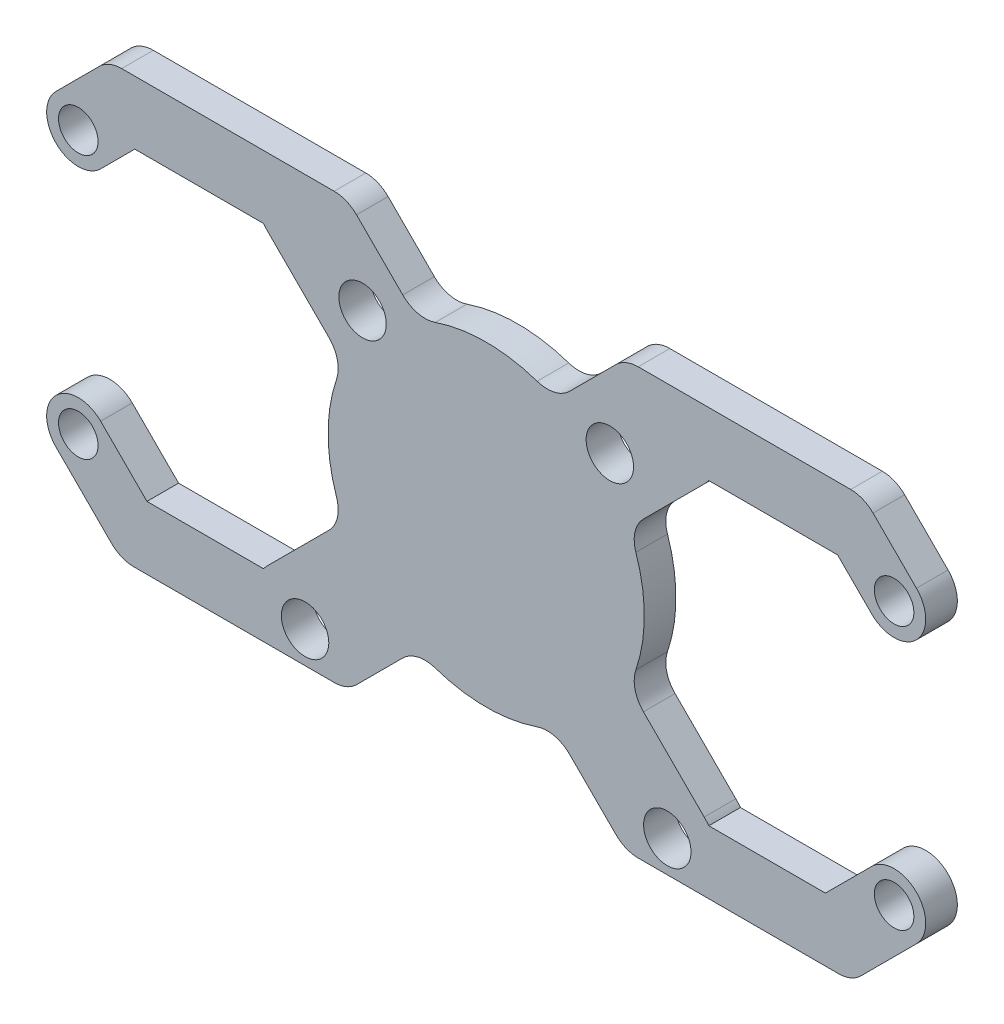
SolidWorks part; units mm, degrees
ref_plane "Front Plane" through (0, 0, 0) normal (0, 0, 1) x (1, 0, 0)
ref_plane "Top Plane" through (0, 0, 0) normal (0, 1, 0) x (1, 0, 0)
ref_plane "Right Plane" through (0, 0, 0) normal (1, 0, 0) x (0, 0, -1)
sketch "Sketch1" plane through (0, 0, 0) normal (0, 0, 1) x (1, 0, 0)
  line L0 (0, -58.2599) -> (0, -50.4392) construction
  line L1 (26.4388, -50.4392) -> (-26.4388, -50.4392) construction
  line L2 (11.4551, -46.8048) -> (23.0548, -46.8048) construction
  line L3 (6.6186, -49.2371) -> (9.0228, -51.6413) construction
  line L4 (11.4551, -44.8048) -> (23.0548, -44.8048)
  line L5 (12.6572, -48.0069) -> (7.7075, -52.9566) construction
  line L6 (5.3033, -50.5524) -> (10.253, -45.6027) construction
  line L7 (-9.0228, -51.6413) -> (-6.6186, -49.2371) construction
  line L8 (-10.253, -45.6027) -> (-5.3033, -50.5524) construction
  line L9 (-7.7075, -52.9566) -> (-12.6572, -48.0069) construction
  line L10 (9.9463, -52.9805) -> (13.7886, -49.1382)
  line L26 (11.4551, -48.8048) -> (23.0548, -48.8048)
  line L27 (23.0548, -46.8048) -> (25.8, -49.55) construction
  line L28 (24.469, -45.3906) -> (27.2142, -48.1358)
  line L29 (21.6406, -48.219) -> (24.3858, -50.9642)
  line L30 (27.5, -54.0885) -> (24.8808, -51.4692) construction
  line L31 (9.9463, -52.9805) -> (13.7886, -49.1382)
  line L39 (-11.4551, -46.8048) -> (-23.0548, -46.8048) construction
  line L40 (-11.4551, -48.8048) -> (-23.0548, -48.8048)
  line L41 (-11.4551, -44.8048) -> (-23.0548, -44.8048)
  line L42 (-23.0548, -46.8048) -> (-25.8, -49.55) construction
  line L43 (-21.6406, -48.219) -> (-24.3858, -50.9642)
  line L44 (-24.469, -45.3906) -> (-27.2142, -48.1358)
  line L45 (-27.5, -54.0885) -> (-24.8808, -51.4692) construction
  line L46 (39.7884, -58.2599) -> (-39.7884, -58.2599) construction
  line L47 (0, -58.2599) -> (0, -69.715) construction
  line L50 (-11.4551, -69.715) -> (11.4551, -69.715) construction
  line L53 (-29.1, -57.875) -> (0, -57.875) construction
  line L56 (-29.1, -56.6635) -> (-29.1, -59.0865) construction
  line L59 (-11.4551, -69.715) -> (-22.285, -69.715) construction
  line L60 (-11.4551, -71.715) -> (-22.285, -71.715)
  line L61 (-11.4551, -67.715) -> (-22.285, -67.715)
  line L62 (-25.8, -66.2) -> (-22.285, -69.715) construction
  line L63 (-24.3858, -64.7858) -> (-20.8708, -68.3008)
  line L64 (-27.2142, -67.6142) -> (-23.6992, -71.1292)
  line L65 (-29.7192, -63.1192) -> (-27.1, -65.7385) construction
  line L66 (25.8, -66.2) -> (22.285, -69.715) construction
  line L67 (13.7886, -67.3816) -> (9.9463, -63.5393)
  line L71 (13.7886, -67.3816) -> (9.9463, -63.5393)
  line L75 (24.3858, -64.7858) -> (20.8708, -68.3008)
  line L76 (27.2142, -67.6142) -> (23.6992, -71.1292)
  line L77 (11.4551, -69.715) -> (22.285, -69.715) construction
  line L78 (11.4551, -71.715) -> (22.285, -71.715)
  line L79 (11.4551, -67.715) -> (22.285, -67.715)
  line L83 (5.2794, -68.2062) -> (9.1217, -72.0485)
  line L85 (5.2794, -68.2062) -> (9.1217, -72.0485)
  line L87 (-9.1217, -72.0485) -> (-5.2794, -68.2062)
  line L89 (-9.1217, -72.0485) -> (-5.2794, -68.2062)
  line L96 (-9.9463, -63.5393) -> (-13.7886, -67.3816)
  line L97 (-9.9463, -63.5393) -> (-13.7886, -67.3816)
  line L98 (-13.7886, -49.1382) -> (-9.9463, -52.9805)
  line L99 (-13.7886, -49.1382) -> (-9.9463, -52.9805)
  line L100 (-5.2794, -48.3136) -> (-9.1217, -44.4713)
  line L101 (-5.2794, -48.3136) -> (-9.1217, -44.4713)
  line L102 (9.1217, -44.4713) -> (5.2794, -48.3136)
  line L103 (9.1217, -44.4713) -> (5.2794, -48.3136)
  arc A0 (11.4551, -44.8048) -> (11.4551, -48.8048) centre (11.4551, -46.8048) ccw
  circle A1 centre (-7.8207, -50.4392) radius 1.5
  circle A2 centre (7.8207, -50.4392) radius 1.5
  circle A3 centre (11.4551, -69.715) radius 1.5
  circle A4 centre (-11.4551, -69.715) radius 1.5
  circle A5 centre (25.8, -49.55) radius 1.25
  arc A6 (27.1, -49.55) -> (24.5, -49.55) centre (25.8, -49.55) ccw construction
  circle A7 centre (-25.8, -49.55) radius 1.25
  arc A8 (-24.5, -49.55) -> (-27.1, -49.55) centre (-25.8, -49.55) ccw construction
  arc A9 (23.0548, -48.8048) -> (23.0548, -44.8048) centre (23.0548, -46.8048) ccw
  arc A10 (24.469, -45.3906) -> (21.6406, -48.219) centre (23.0548, -46.8048) ccw
  arc A11 (24.3858, -50.9642) -> (27.2142, -48.1358) centre (25.8, -49.55) ccw
  arc A12 (-11.4551, -48.8048) -> (-11.4551, -44.8048) centre (-11.4551, -46.8048) ccw
  arc A13 (-23.0548, -44.8048) -> (-23.0548, -48.8048) centre (-23.0548, -46.8048) ccw
  arc A14 (-21.6406, -48.219) -> (-24.469, -45.3906) centre (-23.0548, -46.8048) ccw
  arc A15 (-27.2142, -48.1358) -> (-24.3858, -50.9642) centre (-25.8, -49.55) ccw
  arc A21 (9.9463, -52.9805) -> (9.3605, -54.3948) centre (11.3605, -54.3948) ccw
  arc A29 (9.9463, -52.9805) -> (9.3605, -54.3948) centre (11.3605, -54.3948) ccw
  arc A37 (9.3605, -54.3948) -> (9.4671, -55.0389) centre (11.3605, -54.3948) ccw
  arc A69 (9.3605, -54.3948) -> (9.4671, -55.0389) centre (11.3605, -54.3948) ccw
  arc A77 (9.4671, -61.4809) -> (9.4671, -55.0389) centre (0, -58.2599) ccw
  arc A85 (9.4671, -61.4809) -> (9.4671, -55.0389) centre (0, -58.2599) ccw
  arc A89 (-11.4551, -71.715) -> (-11.4551, -67.715) centre (-11.4551, -69.715) ccw
  arc A90 (-22.285, -67.715) -> (-22.285, -71.715) centre (-22.285, -69.715) ccw
  circle A91 centre (-25.8, -66.2) radius 1.25
  arc A92 (-27.1, -66.2) -> (-24.5, -66.2) centre (-25.8, -66.2) ccw construction
  arc A93 (-24.3858, -64.7858) -> (-27.2142, -67.6142) centre (-25.8, -66.2) ccw
  arc A94 (-23.6992, -71.1292) -> (-20.8708, -68.3008) centre (-22.285, -69.715) ccw
  circle A95 centre (25.8, -66.2) radius 1.25
  arc A96 (24.3858, -64.7858) -> (27.2142, -67.6142) centre (25.8, -66.2) cw
  arc A97 (23.6992, -71.1292) -> (20.8708, -68.3008) centre (22.285, -69.715) cw
  arc A98 (11.4551, -71.715) -> (11.4551, -67.715) centre (11.4551, -69.715) cw
  arc A99 (22.285, -67.715) -> (22.285, -71.715) centre (22.285, -69.715) cw
  arc A113 (9.4671, -61.4809) -> (9.3605, -62.1251) centre (11.3605, -62.1251) ccw
  arc A117 (9.4671, -61.4809) -> (9.3605, -62.1251) centre (11.3605, -62.1251) ccw
  arc A121 (9.3605, -62.1251) -> (9.9463, -63.5393) centre (11.3605, -62.1251) ccw
  arc A125 (9.3605, -62.1251) -> (9.9463, -63.5393) centre (11.3605, -62.1251) ccw
  arc A129 (9.1217, -72.0485) -> (13.7886, -67.3816) centre (11.4551, -69.715) ccw
  arc A142 (9.1217, -72.0485) -> (13.7886, -67.3816) centre (11.4551, -69.715) ccw
  arc A143 (5.2794, -68.2062) -> (3.221, -67.727) centre (3.8652, -69.6204) ccw
  arc A144 (5.2794, -68.2062) -> (3.221, -67.727) centre (3.8652, -69.6204) ccw
  arc A145 (-3.221, -67.727) -> (3.221, -67.727) centre (0, -58.2599) ccw
  arc A146 (-3.221, -67.727) -> (3.221, -67.727) centre (0, -58.2599) ccw
  arc A147 (-3.221, -67.727) -> (-5.2794, -68.2062) centre (-3.8652, -69.6204) ccw
  arc A148 (-3.221, -67.727) -> (-5.2794, -68.2062) centre (-3.8652, -69.6204) ccw
  arc A149 (-14.7551, -69.715) -> (-9.1217, -72.0485) centre (-11.4551, -69.715) ccw
  arc A150 (-14.7551, -69.715) -> (-9.1217, -72.0485) centre (-11.4551, -69.715) ccw
  arc A151 (-13.7886, -67.3816) -> (-14.7551, -69.715) centre (-11.4551, -69.715) ccw
  arc A153 (-13.7886, -67.3816) -> (-14.7551, -69.715) centre (-11.4551, -69.715) ccw
  arc A155 (-9.9463, -63.5393) -> (-9.4671, -61.4809) centre (-11.3605, -62.1251) ccw
  arc A157 (-9.9463, -63.5393) -> (-9.4671, -61.4809) centre (-11.3605, -62.1251) ccw
  arc A159 (-10, -58.2599) -> (-9.4671, -61.4809) centre (0, -58.2599) ccw
  arc A161 (-10, -58.2599) -> (-9.4671, -61.4809) centre (0, -58.2599) ccw
  arc A163 (-9.4671, -55.0389) -> (-10, -58.2599) centre (0, -58.2599) ccw
  arc A165 (-9.4671, -55.0389) -> (-10, -58.2599) centre (0, -58.2599) ccw
  arc A167 (-9.4671, -55.0389) -> (-9.9463, -52.9805) centre (-11.3605, -54.3948) ccw
  arc A169 (-9.4671, -55.0389) -> (-9.9463, -52.9805) centre (-11.3605, -54.3948) ccw
  arc A171 (-11.4551, -43.5048) -> (-13.7886, -49.1382) centre (-11.4551, -46.8048) ccw
  arc A173 (-11.4551, -43.5048) -> (-13.7886, -49.1382) centre (-11.4551, -46.8048) ccw
  arc A174 (-9.1217, -44.4713) -> (-11.4551, -43.5048) centre (-11.4551, -46.8048) ccw
  arc A175 (-9.1217, -44.4713) -> (-11.4551, -43.5048) centre (-11.4551, -46.8048) ccw
  arc A176 (-5.2794, -48.3136) -> (-3.221, -48.7928) centre (-3.8652, -46.8994) ccw
  arc A177 (-5.2794, -48.3136) -> (-3.221, -48.7928) centre (-3.8652, -46.8994) ccw
  arc A178 (3.221, -48.7928) -> (-3.221, -48.7928) centre (0, -58.2599) ccw
  arc A179 (3.221, -48.7928) -> (-3.221, -48.7928) centre (0, -58.2599) ccw
  arc A180 (3.221, -48.7928) -> (5.2794, -48.3136) centre (3.8652, -46.8994) ccw
  arc A181 (3.221, -48.7928) -> (5.2794, -48.3136) centre (3.8652, -46.8994) ccw
  arc A182 (13.7886, -49.1382) -> (9.1217, -44.4713) centre (11.4551, -46.8048) ccw
  arc A183 (13.7886, -49.1382) -> (9.1217, -44.4713) centre (11.4551, -46.8048) ccw
  point P7 (0, -50.4392)
  point P20 (-16.87, -69.715)
  point P37 (7.8207, -50.4392)
  point P43 (-7.8207, -50.4392)
  point P60 (17.255, -46.8048)
  point P67 (24.4274, -48.1774)
  point P73 (-17.255, -46.8048)
  point P83 (-24.4274, -48.1774)
  point P94 (0, -69.715)
  point P101 (0, -58.2599)
  point P115 (-24.0425, -67.9575)
  point P127 (24.0425, -67.9575)
  point P134 (16.87, -69.715)
  dimension "D2" = 3
  dimension "D4" = 2.5
  dimension "D5" = 2.5
  dimension "D9" = 2.5
  dimension "D3" = 7.8207
  dimension "D6" = 4
  dimension "D7" = 4
  dimension "D8" = 4
  dimension "D1" = 0
extrude "Boss-Extrude1" add sketch "Sketch1" along normal blind 2 contours A12 L40 L26 A0 A1 A2 | A12 L40 | L41 A14 L43 L40 | L43 A14 A13 A7 L40 | L44 A15 L43 L40 A13 A7 | A0 L26 | L26 L29 A10 L4 | A9 A10 L29 L26 A5 | L29 A11 L28 A9 A5 L26 | A3 | A4 | A153 L61 L63 A94 L60 A150 | A90 A94 L63 L61 | L63 A93 L64 A90 L61 A91 | A142 L78 A97 L75 L79 | L79 A99 L76 A96 L75 A95 | A99 L79 L75 A97 region at (0, -58.4977, 0) region at (12.1951, -46.8048, 0) region at (18.0104, -46.7989, 0) region at (23.0495, -46.8176, 0) region at (25.7829, -46.8219, 0) region at (-18.0104, -46.7989, 0) region at (-12.1951, -46.8048, 0) region at (-23.0495, -46.8176, 0) region at (14.6887, -69.715, 0) region at (17.6266, -69.7216, 0) region at (-24.9793, -47.6019, 0) region at (22.2797, -69.7022, 0) region at (22.9876, -66.3168, 0) region at (-17.6266, -69.7216, 0) region at (-12.7676, -67.7814, 0) region at (-22.2797, -69.7022, 0) region at (-21.8708, -67.6211, 0)
sketch "Sketch2" plane through (0, -44.8048, 0) normal (0, 1, 0) x (1, 0, 0)
  line L1 (25.3477, 5.303) -> (-25.3477, 5.303)
  line L2 (25.3477, 5.303) -> (25.3477, -5.303)
  line L3 (25.3477, -5.303) -> (-25.3477, -5.303)
  line L4 (-25.3477, 5.303) -> (-25.3477, -5.303)
  line L5 (25.3477, 5.303) -> (-25.3477, -5.303) construction
  line L6 (25.3477, -5.303) -> (-25.3477, 5.303) construction
  point P0 (0, 0)
extrude "Cut-Extrude1" cut sketch "Sketch2" along normal through all
extrude "Cut-Extrude2" cut sketch "Sketch2<2>" against normal through all from surface starting at face at (18.1825, -71.715, 1)
sketch "Sketch2<2>" plane through (0, -44.8048, 0) normal (0, 1, 0) x (1, 0, 0) same geometry as "Sketch2"
fillet "Fillet1" radius 2 4 edges at (8.7882, -44.8048, 1) (-8.7882, -44.8048, 1) (8.7882, -71.715, 1) (-8.7882, -71.715, 1)
